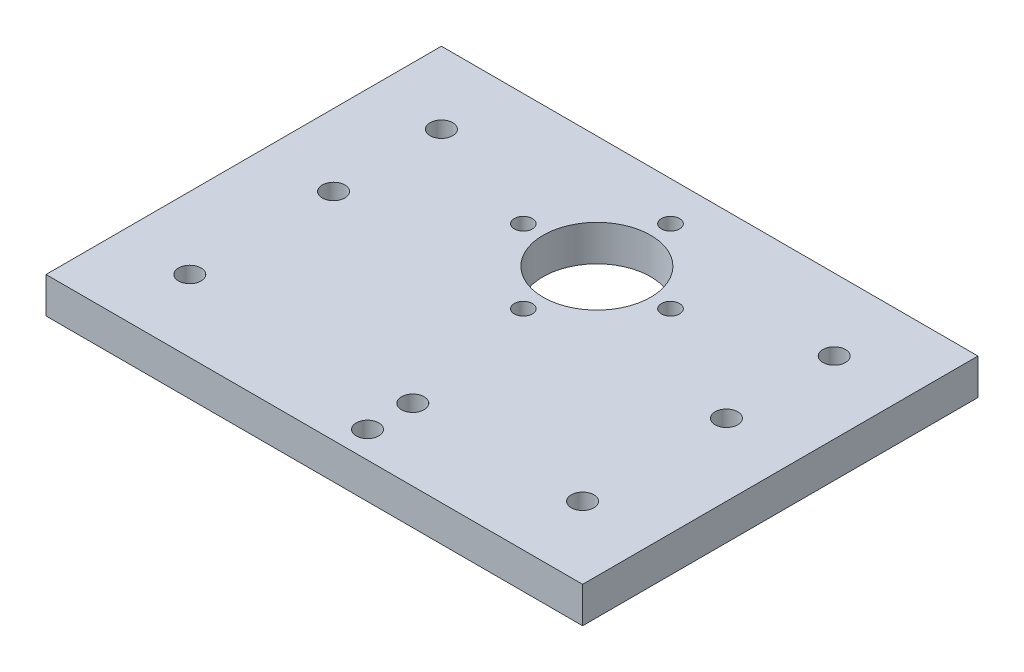
SolidWorks part; units mm, degrees
ref_plane "Front Plane" through (0, 0, 0) normal (0, 0, 1) x (1, 0, 0)
ref_plane "Top Plane" through (0, 0, 0) normal (0, 1, 0) x (1, 0, 0)
ref_plane "Right Plane" through (0, 0, 0) normal (1, 0, 0) x (0, 0, -1)
sketch "Sketch1" plane through (0, 0, 0) normal (0, 1, 0) x (1, 0, 0)
  line L0 (-34.7, 3.175) -> (34.7, 3.175) construction
  line L1 (-47.4, 34.925) -> (47.4, 34.925)
  line L2 (-47.4, 34.925) -> (-47.4, -34.925)
  line L3 (-47.4, -34.925) -> (47.4, -34.925)
  line L4 (47.4, 34.925) -> (47.4, -34.925)
  line L5 (-47.4, 34.925) -> (47.4, -34.925) construction
  line L6 (-47.4, -34.925) -> (47.4, 34.925) construction
  line L7 (22, -34.925) -> (47.4, -34.925) construction
  line L8 (4.7, -30.225) -> (4.7, -22.225) construction
  line L9 (-34.7, -22.225) -> (34.7, -22.225) construction
  line L10 (-34.7, -22.225) -> (-34.7, 22.225) construction
  line L11 (-34.7, 22.225) -> (34.7, 22.225) construction
  line L12 (34.7, -22.225) -> (34.7, 22.225) construction
  line L13 (-34.7, -22.225) -> (34.7, 22.225) construction
  line L14 (-34.7, 22.225) -> (34.7, -22.225) construction
  line L15 (0, 0) -> (0, 15) construction
  line L16 (4.7, -30.225) -> (18.2, -30.225) construction
  line L17 (22, -34.925) -> (22, -9.525) construction
  line L18 (22, -9.525) -> (47.4, -9.525) construction
  line L19 (47.4, -34.925) -> (47.4, -9.525) construction
  line L20 (22, -34.925) -> (47.4, -9.525) construction
  line L21 (22, -9.525) -> (47.4, -34.925) construction
  circle A18 centre (-34.7, 22.225) radius 2
  circle A19 centre (34.7, 22.225) radius 2
  circle A20 centre (34.7, -22.225) radius 2
  circle A21 centre (-34.7, -22.225) radius 2
  circle A22 centre (4.7, -30.225) radius 2
  circle A23 centre (4.7, -22.225) radius 2
  circle A24 centre (0, 15) radius 9.5
  circle A25 centre (0, 15) radius 13 construction
  circle A26 centre (0, 28) radius 1.5 construction
  circle A27 centre (-13, 15) radius 1.5 construction
  circle A28 centre (13, 15) radius 1.5 construction
  circle A29 centre (0, 2) radius 1.5 construction
  circle A30 centre (-34.7, 3.175) radius 2
  circle A31 centre (34.7, 3.175) radius 2
  dimension "D2" = 30
  dimension "D4" = 19
  dimension "D7" = 26
  dimension "D10" = 4
  dimension "D13" = 12.7
  dimension "D15" = 4
  dimension "D16" = 8
  dimension "D17" = 4
  dimension "D9" = 3
  dimension "D5" = 15
  dimension "D6" = 94.8
  dimension "D8" = 69.85
  dimension "D11" = 25.4
  dimension "D14" = 12.7
  dimension "D3" = 13.5
extrude "Boss-Extrude1" add sketch "Sketch1" along normal blind 6.35
hole_wizard "CSK for M3 Flat Head Machine Screw1" positions "Sketch7" profile "Sketch8" countersink size "M3" standard "ANSI Metric" end condition through all
sketch "Sketch7" plane through (0, 0, 0) normal (0, -1, 0) x (-1, 0, 0)
  point P0 (-13, 15)
  point P3 (0, 2)
  point P6 (13, 15)
  point P9 (0, 28)
sketch "Sketch8" plane through (13, 0, -15) normal (1, 0, 0) x (0, 0, -1)
  line L0 (0, 0) -> (0, 6.35)
  line L1 (0, 6.35) -> (1.6, 6.35)
  line L2 (1.6, 6.35) -> (1.6, 1.55)
  line L3 (1.6, 1.55) -> (3.15, 0)
  line L5 (3.15, 0) -> (0, 0)
  line L6 (-1.6, 1.55) -> (-3.15, 0) construction
  line L11 (0, -6.35) -> (0, 107.95) construction
  dimension "Thru Hole Dia." = 3.2
  dimension "Thru Hole Depth" = 6.35
  dimension "Near C'Sink Dia." = 6.3
  dimension "Near C'Sink Angle" = 90
equation "\"testbed_height\" = 91.50mm"
equation "\"plate_thickness\" = 6mm"
equation "\"main_body_splay_length\" = 48.5mm"
equation "\"splay_shaft_length_no_wires\" = 10mm"
equation "\"splay_shaft_length_wires\" = 6.5mm"
equation "\"timing_pulley_offset\" = 0mm"
equation "\"effective_motor_length\" = \"timing_pulley_offset\" + \"splay_shaft_length_no_wires\" + \"main_body_splay_length\""
equation "\"80_20_side\" = 25.4mm"
equation "\"80_20_length\" = 152.4mm"
equation "\"80_20_optic_mount_length\" = \"80_20_length\" - 25.4mm"
equation "\"optic_board_hole_size\" = 6.35mm"
equation "\"total_mounting_length\" = \"testbed_height\" - \"effective_motor_length\" - \"80_20_side\""
equation "\"mounting_vertical_portion_height\" = \"total_mounting_length\" - 2 * \"plate_thickness\""
equation "\"face_mount_width\" = 15.25mm"
equation "\"center_dist_to_face_mount_vertical_screws\" = 5mm"
equation "\"D1@Boss-Extrude1\"=0.25in"
